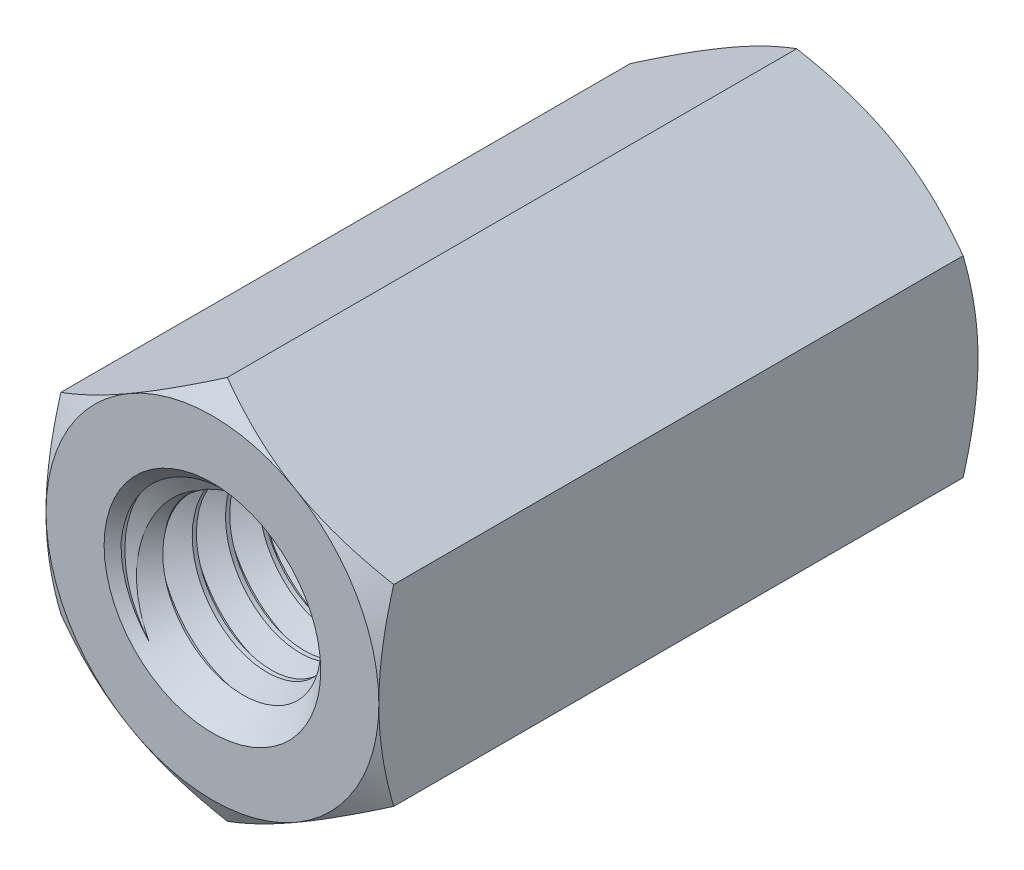
SolidWorks part; units mm, degrees
ref_plane "Front Plane" through (0, 0, 0) normal (0, 0, 1) x (1, 0, 0)
ref_plane "Top Plane" through (0, 0, 0) normal (0, 1, 0) x (1, 0, 0)
ref_plane "Right Plane" through (0, 0, 0) normal (1, 0, 0) x (0, 0, -1)
sketch "Sketch1" plane through (0, 0, 0) normal (0, 0, 1) x (1, 0, 0)
  line L1 (0, 5.7735) -> (-5, 2.8868)
  line L2 (-5, 2.8868) -> (-5, -2.8868)
  line L3 (-5, -2.8868) -> (0, -5.7735)
  line L4 (0, -5.7735) -> (5, -2.8868)
  line L5 (5, -2.8868) -> (5, 2.8868)
  line L6 (5, 2.8868) -> (0, 5.7735)
  circle A0 centre (0, 0) radius 5 construction
  dimension "Hex" = 10
extrude "Extrude1" add sketch "Sketch1" against normal blind 18
sketch "Sketch2" plane through (0, 0, 0) normal (0, 0, 1) x (1, 0, 0)
  circle A0 centre (0, 0) radius 5 construction
  circle A1 centre (0, 0) radius 5
extrude "Cut-Extrude1" cut sketch "Sketch2" against normal through all draft 60 flip side to cut
sketch "Sketch3" plane through (0, 0, -18) normal (0, 0, -1) x (-1, 0, 0)
  circle A1 centre (0, 0) radius 5
  circle A2 centre (0, 0) radius 5
  dimension "D1" = 0
extrude "Cut-Extrude2" cut sketch "Sketch3" against normal through all draft 60 flip side to cut
sketch "Sketch4" plane through (0, 0, 0) normal (0, 0, 1) x (1, 0, 0)
  circle A0 centre (0, 0) radius 3
  dimension "Thread Dia" = 6
extrude "Cut-Extrude3" cut sketch "Sketch4" against normal through all
sketch "Sketch7" plane through (0, 0, 0) normal (0, 0, 1) x (1, 0, 0)
  circle A4 centre (0, 0) radius 3.254
  circle A5 centre (0, 0) radius 3.254
  dimension "D1" = 0.254
sketch "Sketch8" plane through (0, 0, -18) normal (0, 0, -1) x (-1, 0, 0)
  circle A1 centre (0, 0) radius 3.254
  circle A2 centre (0, 0) radius 3.254 construction
sketch "Sketch5" plane through (0, 0, 0) normal (0, 0, 1) x (1, 0, 0)
  circle A0 centre (0, 0) radius 3 construction
  circle A1 centre (0, 0) radius 3
curve "Helix/Spiral1" pitch 1 height 19 turns 19 parameters "pitch"=1
sketch "Sketch9" plane through (0, 0, 0) normal (1, 0, 0) x (0, 0, -1)
  line L0 (-0.5, 3) -> (-0.375, 3)
  line L1 (-0.375, 3) -> (0, 2.3505)
  line L2 (-0.5, 3) -> (-0.875, 2.3505)
  line L3 (-0.875, 2.3505) -> (0, 2.3505)
  line L4 (-0.4375, 3) -> (-0.4375, 2.3505) construction
  line L5 (-0.6875, 2.6752) -> (-0.1875, 2.6752) construction
  line L7 (0, 2.3505) -> (0, 3) construction
  line L8 (0, 3) -> (0, -3) construction
  dimension "D1" = 0.125
  dimension "D2" = 0.5
  dimension "D3" = 60
sketch "Sketch12" plane through (0, 0, 0) normal (0, 0, 1) x (1, 0, 0)
  circle A0 centre (0, 0) radius 2.3505
  circle A1 centre (0, 0) radius 3 construction
  circle A2 centre (0, 0) radius 3
extrude "Extrude2" add sketch "Sketch12" against normal up to surface (18 mm away) up to face at (3, 0, -18)
sweep "Cut-Sweep1" cut profiles "Sketch9" path "Helix/Spiral1"
extrude "Cut-Extrude6" cut sketch "Sketch7" against normal through all draft 45
extrude "Cut-Extrude7" cut sketch "Sketch8" against normal through all draft 45
equation "\"D2@Sketch9\" = \"pitch@Helix/Spiral1\"*.5"
equation "\"D3@Helix/Spiral1\" = \"pitch@Helix/Spiral1\"+\"Height@Extrude1\""
equation "\"D1@Sketch9\" = \"pitch@Helix/Spiral1\"*.125"
